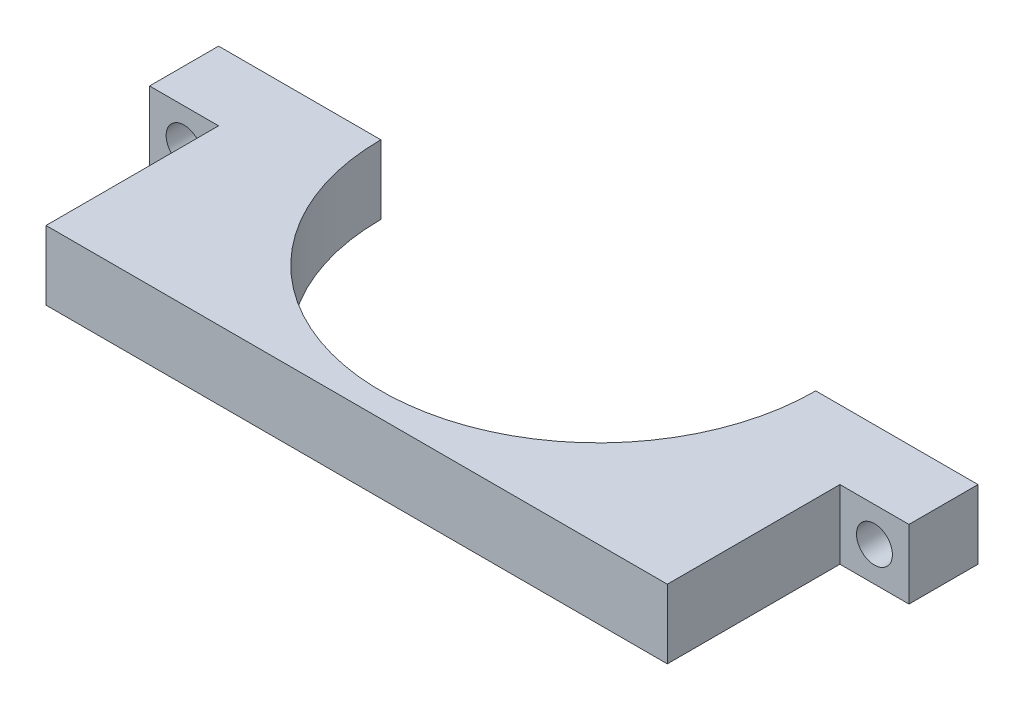
SolidWorks part; units mm, degrees
ref_plane "Front Plane" through (0, 0, 0) normal (0, 0, 1) x (1, 0, 0)
ref_plane "Top Plane" through (0, 0, 0) normal (0, 1, 0) x (1, 0, 0)
ref_plane "Right Plane" through (0, 0, 0) normal (1, 0, 0) x (0, 0, -1)
sketch "Sketch1" plane through (0, 0, 0) normal (0, 1, 0) x (1, 0, 0)
  line L0 (0, 0) -> (-19.4034, 0) construction
  line L1 (-31.6228, 0) -> (-61.4678, 0)
  line L2 (-61.4678, 0) -> (-61.4678, -12.7)
  line L3 (-61.4678, -12.7) -> (-48.7678, -12.7)
  line L4 (-48.7678, -12.7) -> (-48.7678, -44.45)
  line L5 (-48.7678, -44.45) -> (65.5322, -44.45)
  line L6 (65.5322, -44.45) -> (65.5322, -12.7)
  line L7 (65.5322, -12.7) -> (78.2322, -12.7)
  line L8 (78.2322, -12.7) -> (78.2322, 0)
  line L9 (78.2322, 0) -> (48.3872, 0)
  arc A0 (-31.6228, 0) -> (48.3872, 0) centre (8.3822, 0) ccw
  dimension "D1" = 29.845
  dimension "D2" = 29.845
  dimension "D3" = 12.7
  dimension "D4" = 12.7
  dimension "D5" = 12.7
  dimension "D6" = 12.7
  dimension "D7" = 31.75
  dimension "D8" = 114.3
  dimension "D9" = 80.01
extrude "Boss-Extrude1" add sketch "Sketch1" along normal blind 12.7
sketch "Sketch2" plane through (0, 0, 12.7) normal (0, 0, 1) x (1, 0, 0)
  line L0 (78.2322, 12.7) -> (78.2322, 0) construction
  line L1 (65.5322, 0) -> (78.2322, 0) construction
  line L2 (-61.4678, 0) -> (-48.7678, 0) construction
  line L3 (-61.4678, 12.7) -> (-61.4678, 0) construction
  circle A0 centre (71.8822, 6.35) radius 3.302
  circle A1 centre (-55.1178, 6.35) radius 3.302
  dimension "D1" = 6.35
  dimension "D2" = 6.35
  dimension "D3" = 6.35
  dimension "D4" = 6.35
extrude "Cut-Extrude1" cut sketch "Sketch2" against normal up to next
